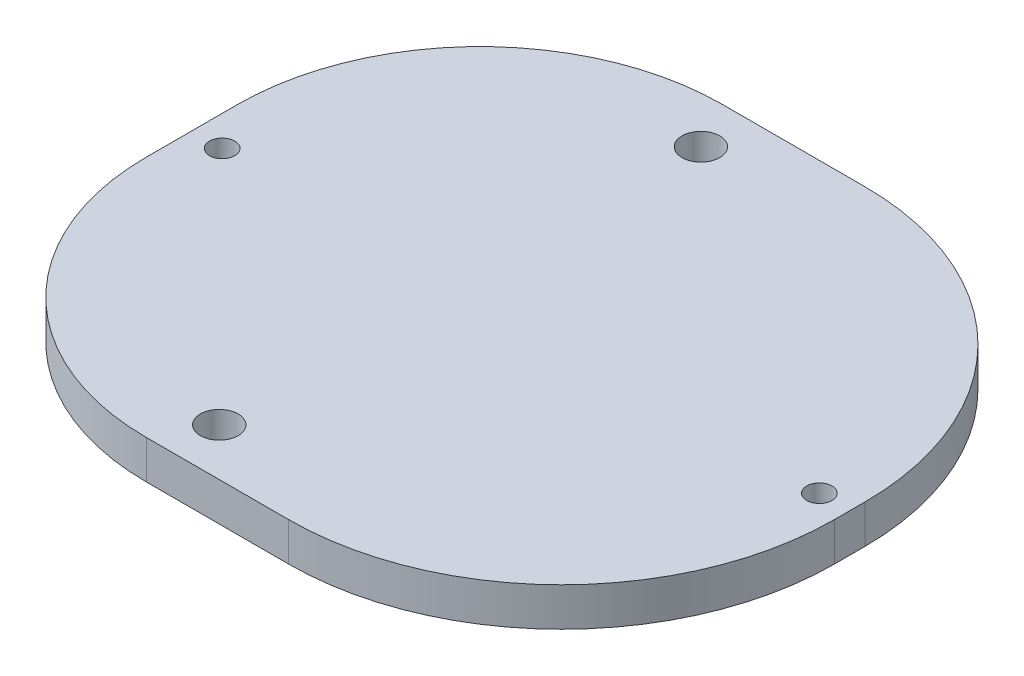
SolidWorks part; units mm, degrees
ref_plane "Front Plane" through (0, 0, 0) normal (0, 0, 1) x (1, 0, 0)
ref_plane "Top Plane" through (0, 0, 0) normal (0, 1, 0) x (1, 0, 0)
ref_plane "Right Plane" through (0, 0, 0) normal (1, 0, 0) x (0, 0, -1)
sketch "Sketch1" plane through (0, 0, 0) normal (0, 1, 0) x (1, 0, 0)
  line L0 (-49.2125, 0) -> (0, 0) construction
  line L1 (-14.2125, -47.5) -> (9.2125, -47.5)
  line L2 (-54.2125, -7.5) -> (-54.2125, 7.5)
  line L3 (-14.2125, 47.5) -> (9.2125, 47.5)
  line L4 (54.2125, -2.5) -> (54.2125, 2.5)
  line L5 (-54.2125, -47.5) -> (54.2125, 47.5) construction
  line L6 (-54.2125, 47.5) -> (54.2125, -47.5) construction
  line L7 (0, 0) -> (49.2125, 0) construction
  line L24 (-10, -47.5) -> (-10, 0) construction
  line L31 (-10, 0) -> (-10, 47.5) construction
  line L32 (-10, -39.6875) -> (-10, 0) construction
  line L33 (-10, 0) -> (-10, 39.6875) construction
  line L34 (-32.5, -32.5) -> (-15, -47.5) construction
  line L35 (12.5, -32.5) -> (12.5, 32.5) construction
  line L36 (-32.5, -32.5) -> (12.5, -32.5) construction
  line L37 (-32.5, -32.5) -> (-32.5, 32.5) construction
  line L38 (-32.5, 32.5) -> (12.5, 32.5) construction
  line L39 (12.5, -32.5) -> (-32.5, 32.5) construction
  line L40 (-32.5, -32.5) -> (12.5, 32.5) construction
  line L41 (-15, -47.5) -> (-5, -47.5) construction
  line L42 (-10, -32.5) -> (-10, -47.5) construction
  line L43 (-5, -47.5) -> (12.5, -32.5) construction
  line L44 (12.5, 32.5) -> (-5, 47.5) construction
  line L45 (-5, 47.5) -> (-15, 47.5) construction
  line L46 (-15, 47.5) -> (-32.5, 32.5) construction
  line L47 (-10, 47.5) -> (-10, 32.5) construction
  circle A0 centre (-49.2125, 0) radius 2.0828
  circle A1 centre (49.2125, 0) radius 2.0828
  arc A4 (-54.2125, 7.5) -> (-14.2125, 47.5) centre (-14.2125, 7.5) cw
  arc A5 (-14.2125, -47.5) -> (-54.2125, -7.5) centre (-14.2125, -7.5) cw
  arc A6 (54.2125, -2.5) -> (9.2125, -47.5) centre (9.2125, -2.5) cw
  arc A7 (9.2125, 47.5) -> (54.2125, 2.5) centre (9.2125, 2.5) cw
  circle A12 centre (-10, -39.6875) radius 3.11
  circle A13 centre (-10, 39.6875) radius 3.11
  point P0 (0, 0)
  point P45 (-10, 0)
  point P75 (-10, -47.5)
  point P77 (-10, 47.5)
  dimension "D4" = 65
  dimension "D9" = 40
  dimension "D10" = 40
  dimension "D11" = 45
  dimension "D12" = 45
  dimension "D17" = 6.22
  dimension "D7" = 4.1656
  dimension "D1" = 98.425
  dimension "D3" = 10
  dimension "D5" = 5
  dimension "D6" = 0
  dimension "D8" = 95
  dimension "D18" = 79.375
  dimension "D20" = 45
  dimension "D23" = 10
  dimension "D24" = 15
extrude "Boss-Extrude1" add sketch "Sketch1" along normal blind 6.35
